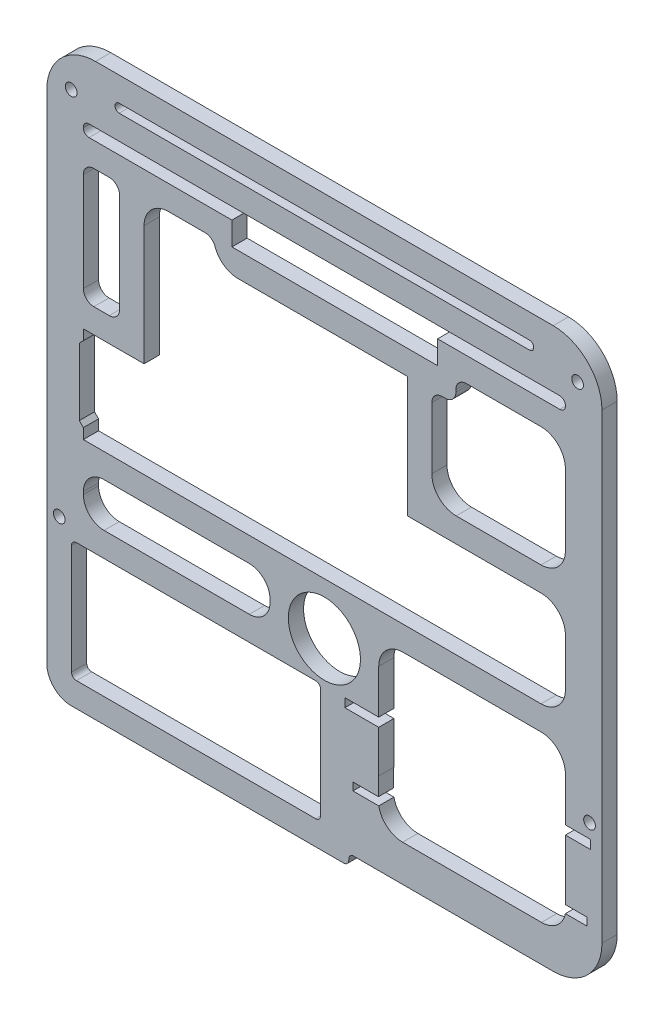
SolidWorks part; units mm, degrees
ref_plane "Front Plane" through (0, 0, 0) normal (0, 0, 1) x (1, 0, 0)
ref_plane "Top Plane" through (0, 0, 0) normal (0, 1, 0) x (1, 0, 0)
ref_plane "Right Plane" through (0, 0, 0) normal (1, 0, 0) x (0, 0, -1)
sketch "Sketch1" plane through (0, 0, 0) normal (0, 0, 1) x (1, 0, 0)
  line L0 (63.9883, 50.6392) -> (63.9883, 46.8292) construction
  line L1 (6.1648, -7.651) -> (64.0322, -7.651)
  line L2 (6.1648, -7.651) -> (6.1648, 50.6392)
  line L3 (6.1648, 50.6392) -> (64.0322, 50.6392)
  line L4 (64.0322, -7.651) -> (64.0322, 50.6392)
  line L5 (60.2222, 46.8292) -> (9.9748, 46.8292)
  line L6 (60.2222, 46.8292) -> (60.2222, -3.841)
  line L7 (60.2222, -3.841) -> (9.9748, -3.841)
  line L8 (9.9748, 46.8292) -> (9.9748, -3.841)
  line L9 (63.9883, 48.7342) -> (18.0707, 48.7342) construction
  line L10 (9.9748, 39.3805) -> (6.1648, 39.3805) construction
  line L11 (8.0698, 39.3805) -> (8.0698, 23.9527) construction
  line L12 (13.5248, -3.841) -> (13.5248, -7.651) construction
  line L13 (13.5248, -5.746) -> (21.1598, -5.746) construction
  line L14 (64.0322, 38.1916) -> (60.2222, 38.1916) construction
  line L15 (62.1272, 38.1916) -> (62.1272, 22.3321) construction
  line L16 (48.6748, 48.7342) -> (23.5288, 48.7342) construction
  line L17 (62.1272, 27.1202) -> (62.1272, 39.363) construction
  line L18 (8.0698, 15.868) -> (8.0698, 3.6252) construction
  line L19 (35.2413, -5.746) -> (34.6952, -5.746) construction
  dimension "D1" = 3.81
  dimension "D2" = 3.81
extrude "Boss-Extrude1" add sketch "Sketch1" along normal blind 1.5875
sketch "Sketch2" plane through (0, 0, 0) normal (0, 0, -1) x (-1, 0, 0)
  line L0 (-60.2222, -3.841) -> (-60.2222, 46.8292) construction
  line L1 (-60.2222, 15.868) -> (-9.9748, 15.868)
  line L2 (-60.2222, 15.868) -> (-60.2222, 13.328)
  line L3 (-60.2222, 13.328) -> (-9.9748, 13.328)
  line L4 (-9.9748, 15.868) -> (-9.9748, 13.328)
  line L5 (-9.9748, 46.8292) -> (-9.9748, -3.841) construction
  line L6 (-13.0532, 15.868) -> (-50.7532, 15.868) construction
  line L8 (-46.8968, 40.9999) -> (-46.8968, 43.4256) construction
  line L9 (-25.4592, 40.9999) -> (-46.8968, 40.9999) construction
  line L10 (-25.4592, 40.9999) -> (-25.4592, 43.4256) construction
  line L11 (-60.2222, 43.4256) -> (-46.8968, 43.4256)
  line L12 (-60.2222, 43.4256) -> (-60.2222, 40.8856)
  line L13 (-60.2222, 40.8856) -> (-48.8018, 40.8856)
  line L14 (-9.9748, 43.4256) -> (-9.9748, 40.8856)
  line L15 (-60.2222, 46.8292) -> (-9.9748, 46.8292)
  line L16 (-60.2222, 46.8292) -> (-60.2222, 44.6575)
  line L17 (-60.2222, 44.6575) -> (-9.9748, 44.6575)
  line L18 (-9.9748, 46.8292) -> (-9.9748, 44.6575)
  line L19 (-60.2222, 46.8292) -> (-9.9748, 46.8292) construction
  line L20 (-55.2788, 43.4256) -> (-16.9248, 43.4256) construction
  line L21 (-55.2788, 44.6575) -> (-16.9248, 44.6575) construction
  line L22 (-46.8968, 40.9999) -> (-46.8968, 43.4256)
  line L23 (-25.4592, 40.9999) -> (-46.8968, 40.9999)
  line L24 (-25.4592, 40.9999) -> (-25.4592, 43.4256)
  line L25 (-48.8018, 40.8856) -> (-48.8018, 38.4599)
  line L26 (-48.8018, 38.4599) -> (-23.5542, 38.4599)
  line L27 (-23.5542, 38.4599) -> (-23.5542, 40.8856)
  line L28 (-23.5542, 40.8856) -> (-9.9748, 40.8856)
  line L29 (-25.4592, 43.4256) -> (-9.9748, 43.4256)
  dimension "D1" = 2.54
  dimension "D2" = 1.905
  dimension "D3" = 2.54
  dimension "D4" = 1.905
extrude "Boss-Extrude2" add sketch "Sketch2" against normal up to surface (1.5875 mm away) up to face at (35.0985, 21.4941, 1.5875)
sketch "Sketch3" plane through (0, 0, 0) normal (0, 0, -1) x (-1, 0, 0)
  line L0 (-50.7532, 25.868) -> (-43.7532, 25.868) construction
  line L1 (-50.7532, 25.868) -> (-43.7532, 25.868)
  line L2 (-50.7532, 25.868) -> (-60.2222, 25.868)
  line L3 (-60.2222, 15.868) -> (-60.2222, 40.8856) construction
  line L4 (-60.2222, 25.868) -> (-60.2222, 28.408)
  line L5 (-60.2222, 28.408) -> (-46.2932, 28.408)
  line L6 (-43.7532, 28.408) -> (-43.7532, 25.868)
  line L7 (-43.7532, 28.408) -> (-43.7532, 38.4599)
  line L8 (-48.8018, 38.4599) -> (-23.5542, 38.4599) construction
  line L9 (-43.7532, 38.4599) -> (-46.2932, 38.4599)
  line L10 (-46.2932, 38.4599) -> (-46.2932, 28.408)
  line L11 (-16.3032, 25.868) -> (-13.0532, 25.868) construction
  line L12 (-16.3032, 25.868) -> (-13.0532, 25.868)
  line L13 (-13.0532, 25.868) -> (-9.9748, 25.868)
  line L14 (-9.9748, 40.8856) -> (-9.9748, 15.868) construction
  line L15 (-9.9748, 25.868) -> (-9.9748, 28.408)
  line L16 (-9.9748, 28.408) -> (-13.7632, 28.408)
  line L17 (-13.7632, 28.408) -> (-13.7632, 40.8856)
  line L18 (-23.5542, 40.8856) -> (-9.9748, 40.8856) construction
  line L19 (-13.7632, 40.8856) -> (-16.3032, 40.8856)
  line L20 (-16.3032, 40.8856) -> (-16.3032, 25.868)
  line L21 (-16.3032, 25.868) -> (-16.2412, 25.8471)
  line M22 (-60.2222, 15.868) -> (-60.2222, 40.8856)
  line M25 (-48.8018, 38.4599) -> (-23.5542, 38.4599)
  line M27 (-23.5542, 40.8856) -> (-9.9748, 40.8856)
  line M28 (-9.9748, 40.8856) -> (-9.9748, 15.868)
  dimension "D1" = 2.54
  dimension "D2" = 2.54
  dimension "D3" = 2.54
  dimension "D4" = 2.54
extrude "Boss-Extrude3" add sketch "Sketch3" against normal up to surface (1.5875 mm away) contours L10 L5 L2 L1 L6 L7 M25 M22 | L20 L12 L13 L16 L17 M27 M28 region at (55.4877, 26.0754, 0) region at (14.3957, 32.1201, 0) up to face at (35.6382, 43.1272, 1.5875)
sketch "Sketch4" plane through (0, 0, 0) normal (0, 0, -1) x (-1, 0, 0)
  line L0 (-60.2222, 13.328) -> (-9.9748, 13.328) construction
  line L1 (-40.7627, 13.328) -> (-29.4343, 13.328)
  line L2 (-40.7627, 13.328) -> (-40.7627, -3.841)
  line L3 (-40.7627, -3.841) -> (-29.4343, -3.841)
  line L4 (-29.4343, 13.328) -> (-29.4343, -3.841)
  line L5 (-9.9748, -3.841) -> (-60.2222, -3.841) construction
  line L6 (-38.8577, 10.4578) -> (-40.7627, 10.4578) construction
  line L7 (-31.3393, 10.4578) -> (-29.4343, 10.4578) construction
  circle A0 centre (-35.0985, 10.4578) radius 3.7592 construction
  dimension "D1" = 1.905
extrude "Boss-Extrude4" add sketch "Sketch4" against normal up to surface (1.5875 mm away) up to face at (11.869, 34.6468, 1.5875)
sketch "Sketch5" plane through (0, 0, 0) normal (0, 0, -1) x (-1, 0, 0)
  line L0 (-8.7364, 6.2047) -> (-34.6952, 6.2047) construction
  line L3 (-34.6952, -6.254) -> (-34.6952, 6.2047) construction
  line L4 (-8.7364, -6.254) -> (-34.6952, -6.254) construction
  line L5 (-8.7364, -6.254) -> (-8.7364, 6.2047) construction
  line L6 (-8.7364, 6.2047) -> (-34.6952, 6.2047)
  line L7 (-34.6952, -6.254) -> (-34.6952, 6.2047)
  line L8 (-8.7364, -6.254) -> (-34.6952, -6.254)
  line L9 (-8.7364, -6.254) -> (-8.7364, 6.2047)
  circle A0 centre (-35.0985, 10.4578) radius 3.7592 construction
  circle A1 centre (-35.0985, 10.4578) radius 3.7592
extrude "Cut-Extrude1" cut sketch "Sketch5" against normal up to surface (1.5875 mm away) up to face at (50.4924, 4.7435, 1.5875)
sketch "Sketch8" plane through (0, 0, 0) normal (0, 0, -1) x (-1, 0, 0)
  line L0 (-9.9748, 13.328) -> (-9.9748, 6.2047) construction
  line L1 (-29.4343, 6.2047) -> (-9.9748, 6.2047)
  line L2 (-29.4343, 6.2047) -> (-29.4343, 8.7447)
  line L3 (-29.4343, 8.7447) -> (-9.9748, 8.7447)
  line L4 (-9.9748, 6.2047) -> (-9.9748, 8.7447)
  dimension "D1" = 2.54
extrude "Boss-Extrude5" add sketch "Sketch8" against normal up to surface (1.5875 mm away) up to face at (31.3393, 10.4578, 1.5875)
fillet "Fillet1" radius 5.08 3 edges at (64.0322, -7.651, 0.7937) (6.1648, 50.6392, 0.7937) (64.0322, 50.6392, 0.7937)
fillet "Fillet2" radius 2.54 7 edges at (16.3032, 40.8856, 0.7937) (23.5542, 38.4599, 0.7937) (60.2222, 40.8856, 0.7937) (46.2932, 28.408, 0.7938) (60.2222, 15.868, 0.7937) (60.2222, 28.408, 0.7937) (60.2222, 25.868, 0.7937)
fillet "Fillet3" radius 1.0922 8 edges at (46.2932, 38.4599, 0.7937) (48.8018, 38.4599, 0.7937) (48.8018, 40.8856, 0.7937) (9.9748, 28.408, 0.7937) (13.7632, 28.408, 0.7937) (9.9748, 40.8856, 0.7937) (13.7632, 40.8856, 0.7937) (23.5542, 40.8856, 0.7937)
fillet "Fillet4" radius 0.5842 4 edges at (9.9748, 43.4256, 0.7937) (9.9748, 44.6575, 0.7937) (60.2222, 44.6575, 0.7937) (60.2222, 43.4256, 0.7937)
fillet "Fillet8" radius 2.159 4 edges at (29.4343, 8.7447, 0.7937) (29.4343, 13.328, 0.7937) (9.9748, 13.328, 0.7937) (9.9748, 8.7447, 0.7937)
sketch "Sketch6" plane through (0, 0, 0) normal (0, 0, -1) x (-1, 0, 0)
  line L0 (-9.5532, 17.368) -> (-11.0532, 15.868) construction
  line L1 (-11.0532, 25.868) -> (-9.5532, 24.368) construction
  line L2 (-9.5532, 24.368) -> (-9.5532, 17.368) construction
  line L3 (-9.5532, 17.368) -> (-11.0532, 15.868)
  line L4 (-11.0532, 25.868) -> (-9.5532, 24.368)
  line L5 (-9.5532, 24.368) -> (-9.5532, 17.368)
  line L6 (-11.0532, 25.868) -> (-11.0532, 15.868)
  circle A4 centre (-61.4922, 46.8292) radius 0.6096 construction
  circle A5 centre (-61.4922, 46.8292) radius 0.6096
  circle A6 centre (-7.4602, 7.6638) radius 0.6096 construction
  circle A7 centre (-7.4602, 7.6638) radius 0.6096
  circle A8 centre (-62.7368, 7.6638) radius 0.6096 construction
  circle A9 centre (-62.7368, 7.6638) radius 0.6096
  circle A10 centre (-8.7048, 46.8292) radius 0.6096 construction
  circle A11 centre (-8.7048, 46.8292) radius 0.6096
extrude "Cut-Extrude2" cut sketch "Sketch6" against normal up to surface (1.5875 mm away) up to face at (21.7158, -0.0246, 1.5875)
sketch "Sketch7" plane through (0, 0, 0) normal (0, 0, -1) x (-1, 0, 0)
  line L0 (-37.2352, 6.2047) -> (-62.813, 6.2047) construction
  line L1 (-62.813, 6.2047) -> (-62.813, 5.2903) construction
  line L2 (-62.813, 5.2903) -> (-37.2352, 5.2903) construction
  line L3 (-37.2352, 5.2903) -> (-37.2352, 6.2047) construction
  line L4 (-38.0692, -0.9917) -> (-62.4532, -0.9917) construction
  line L5 (-62.4532, -0.9917) -> (-62.4532, -1.8045) construction
  line L6 (-62.4532, -1.8045) -> (-38.0692, -1.8045) construction
  line L7 (-38.0692, -1.8045) -> (-38.0692, -0.9917) construction
  line L8 (-37.2352, 6.2047) -> (-62.813, 6.2047)
  line L9 (-62.813, 6.2047) -> (-62.813, 5.2903)
  line L10 (-62.813, 5.2903) -> (-37.2352, 5.2903)
  line L11 (-37.2352, 5.2903) -> (-37.2352, 6.2047)
  line L12 (-38.0692, -0.9917) -> (-62.4532, -0.9917)
  line L13 (-62.4532, -0.9917) -> (-62.4532, -1.8045)
  line L14 (-62.4532, -1.8045) -> (-38.0692, -1.8045)
  line L15 (-38.0692, -1.8045) -> (-38.0692, -0.9917)
  line L20 (-59.7862, -0.9917) -> (-40.7362, -0.9917)
  line L21 (-40.7362, -0.9917) -> (-40.7362, 0.8879)
  line L22 (-40.7362, 0.8879) -> (-59.7862, 0.8879)
  line L23 (-59.7862, 0.8879) -> (-59.7862, -0.9917)
  line L24 (-59.7862, -0.9917) -> (-40.7362, -0.9917)
  line L25 (-40.7362, -0.9917) -> (-40.7362, 0.8879)
  line L26 (-40.7362, 0.8879) -> (-59.7862, 0.8879)
  line L27 (-59.7862, 0.8879) -> (-59.7862, -0.9917)
  dimension "D1" = 0
extrude "Cut-Extrude3" cut sketch "Sketch7" against normal up to surface (1.5875 mm away) contours L14 L15 L12 L13 | L26 L27 L12 L25 | L10 L11 L8 L9 region at (50.0241, 5.7475, 0) region at (50.2612, -1.3981, 0) region at (50.2612, -0.0519, 0) up to face at (8.0952, 46.8292, 1.5875)
fillet "Fillet6" radius 0.508 4 edges at (34.6952, 6.2047, 0.7937) (34.6952, -6.254, 0.7937) (8.7364, -6.254, 0.7937) (8.7364, 6.2047, 0.7937)
sketch "Sketch9" plane through (0, 0, 1.5875) normal (0, 0, 1) x (1, 0, 0)
  line L0 (58.9522, 50.6392) -> (11.2448, 50.6392) construction
  line L1 (13.2768, 48.0992) -> (56.9202, 48.0992)
  line L2 (13.2768, 48.0992) -> (13.2768, 47.1975)
  line L3 (13.2768, 47.1975) -> (56.9202, 47.1975)
  line L8 (56.9202, 48.0992) -> (56.9202, 47.1975)
  line L9 (10.559, 44.6575) -> (59.638, 44.6575) construction
  line L10 (6.1648, 45.5592) -> (6.1648, 59.3208) construction
  line L11 (13.2768, 48.0992) -> (6.1648, 48.0992) construction
  line L13 (56.9202, 48.0992) -> (64.0322, 48.0992) construction
  line L14 (64.0322, 45.5592) -> (64.0322, 56.8419) construction
  dimension "D1" = 2.54
  dimension "D2" = 2.54
  dimension "D3" = 7.112
extrude "Cut-Extrude4" cut sketch "Sketch9" against normal up to surface (1.5875 mm away) up to face at (49.4783, 2.5248, 0)
fillet "Fillet7" radius 0.4318 4 edges at (13.2768, 47.1975, 0.7937) (13.2768, 48.0992, 0.7937) (56.9202, 47.1975, 0.7937) (56.9202, 48.0992, 0.7937)
fillet "Fillet9" radius 2.54 4 edges at (60.2222, -3.841, 0.7937) (40.7627, -3.841, 0.7937) (60.2222, 13.328, 0.7937) (40.7627, 13.328, 0.7937)
sketch "Sketch10" plane through (0, 0, 1.5875) normal (0, 0, 1) x (1, 0, 0)
  line L0 (35.0985, 14.217) -> (35.0985, -13.4858) construction
  line L1 (6.1648, -7.651) -> (37.6385, -7.651)
  line L2 (6.1648, -7.651) -> (6.1648, -8.794)
  line L3 (6.1648, -8.794) -> (37.6385, -8.794)
  line L4 (37.6385, -7.651) -> (37.6385, -8.794)
  line L5 (9.2444, -6.254) -> (34.1872, -6.254) construction
  circle A0 centre (35.0985, 10.4578) radius 3.7592 construction
  dimension "D1" = 2.54
  dimension "D2" = 2.54
extrude "Boss-Extrude6" add sketch "Sketch10" against normal up to surface (1.5875 mm away) up to face at (35.0985, 47.6484, 0)
fillet "Fillet10" radius 2.54 1 edges at (6.1648, -8.794, 0.7937)
fillet "Fillet11" radius 0.508 2 edges at (37.6385, -7.651, 0.7937) (37.6385, -8.794, 0.7937)
